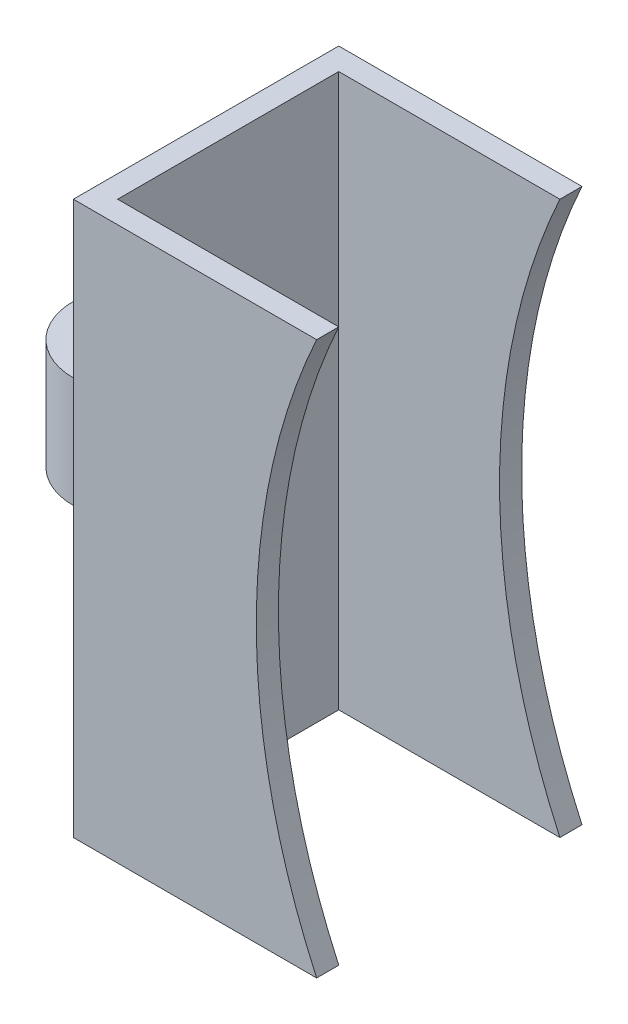
SolidWorks part; units mm, degrees
ref_plane "Front Plane" through (0, 0, 0) normal (0, 0, 1) x (1, 0, 0)
ref_plane "Top Plane" through (0, 0, 0) normal (0, 1, 0) x (1, 0, 0)
ref_plane "Right Plane" through (0, 0, 0) normal (1, 0, 0) x (0, 0, -1)
sketch "Sketch1" plane through (0, 0, 0) normal (0, 1, 0) x (1, 0, 0)
  line L0 (0, 0) -> (0, 20)
  line L1 (0, 20) -> (20, 20)
  line L2 (0, 0) -> (20, 0)
  line L3 (-2, -2) -> (20, -2)
  line L4 (-2, -2) -> (-2, 22)
  line L5 (-2, 22) -> (20, 22)
  line L6 (20, 20) -> (20, 22)
  line L7 (20, 0) -> (20, -2)
  dimension "D1" = 20
  dimension "D2" = 20
  dimension "D3" = 20
  dimension "D4" = 2
extrude "Boss-Extrude1" add sketch "Sketch1" along normal blind 50
sketch "Sketch3" plane through (0, 0, -22) normal (0, 0, -1) x (-1, 0, 0)
  circle A0 centre (-74.5436, 25) radius 60
  dimension "D1" = 120
extrude "Cut-Extrude1" cut sketch "Sketch3" against normal through all both and the other way through all
sketch "Sketch4" plane through (0, 50, 0) normal (0, 1, 0) x (1, 0, 0)
  line L0 (-2, 10) -> (-11.6031, 10) construction
  line L1 (-2, 22) -> (-2, -2) construction
  circle A0 centre (-8, 10) radius 4
  circle A1 centre (-8, 10) radius 6
  point P4 (-8.5685, 10.4312)
  point P5 (0, 0)
  dimension "D1" = 8
  dimension "D2" = 2
extrude "Boss-Extrude2" add sketch "Sketch4" along normal blind 10 from offset 30 separate body offset against normal yes
